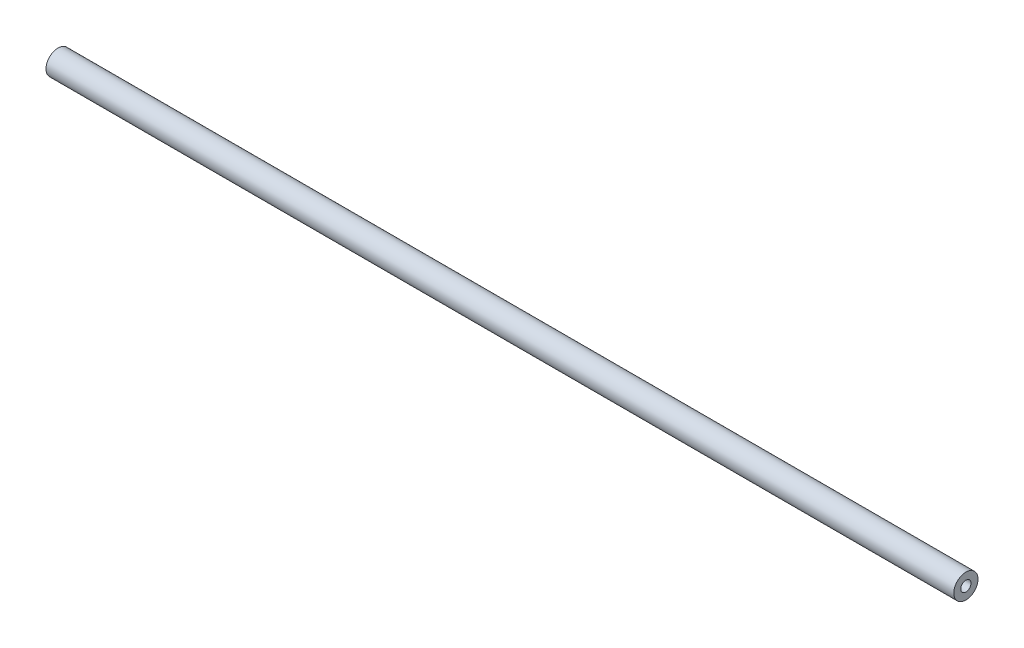
SolidWorks part; units mm, degrees
material "7075-T6 (SN)"
ref_plane "Front Plane" through (0, 0, 0) normal (0, 0, 1) x (1, 0, 0)
ref_plane "Top Plane" through (0, 0, 0) normal (0, 1, 0) x (1, 0, 0)
ref_plane "Right Plane" through (0, 0, 0) normal (1, 0, 0) x (0, 0, -1)
sketch "Sketch1" plane through (0, 0, 0) normal (1, 0, 0) x (0, 0, -1)
  circle A1 centre (0, 0) radius 4.7625
  dimension "D1" = 9.525
extrude "Boss-Extrude1" add sketch "Sketch1" along normal mid plane 357.1875 contours A1 region at (0, 0, 0)
hole_wizard "#10-32 Tapped Hole1" positions "3DSketch1" profile "Sketch2" tap size "#10-32" standard "ANSI Inch"
sketch3d "3DSketch1"
  line L0 (178.5938, 0, 0) -> (-178.5938, 0, 0) construction
  point P0 (178.5938, 0, 0)
  point P7 (-178.5938, 0, 0)
sketch "Sketch2" plane through (178.5938, 0, 0) normal (0, 1, 0) x (0, 0, -1)
  line L0 (0, 0) -> (0, 13.2428)
  line L1 (0, 13.2428) -> (2.0193, 12.0294)
  line L2 (2.0193, 12.0294) -> (2.0193, 0)
  line L5 (2.0193, 0) -> (0, 0)
  line L10 (0, 13.2428) -> (-2.0193, 12.0294) construction
  line L11 (0, -6.35) -> (0, 107.95) construction
  dimension "Tap Drill Dia." = 4.0386
  dimension "Tap Drill Depth" = 12.0294
  dimension "Drill Angle" = 118
cosmetic thread "Hole Thread1"
cosmetic thread "Hole Thread2"
